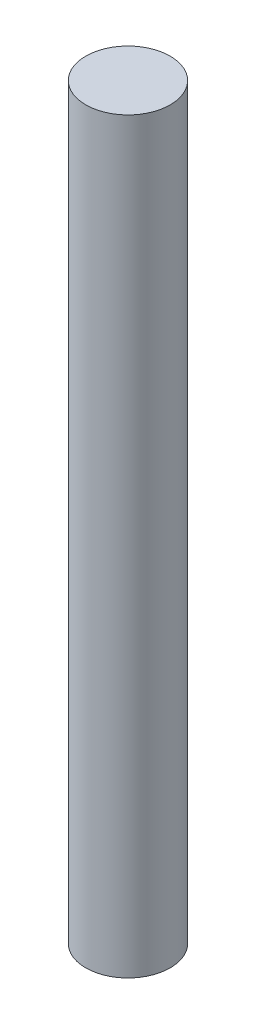
SolidWorks part; units mm, degrees
ref_plane "Alzado" through (0, 0, 0) normal (0, 0, 1) x (1, 0, 0)
ref_plane "Planta" through (0, 0, 0) normal (0, 1, 0) x (1, 0, 0)
ref_plane "Vista lateral" through (0, 0, 0) normal (1, 0, 0) x (0, 0, -1)
sketch "Croquis1" plane through (0, 0, 0) normal (0, 1, 0) x (1, 0, 0)
  circle A0 centre (0, 0) radius 4
  dimension "D1" = 8
extrude "Saliente-Extruir1" add sketch "Croquis1" along normal blind 100
ref_plane "Plano1" through (1.8651, 0, 3.5386) normal (0.4663, 0, 0.8846) x (0.8846, 0, -0.4663)
ref_plane "Plano2" through (1.8651, 0, 3.5386) normal (0.4663, 0, 0.8846) x (0.8846, 0, -0.4663)
sketch "Croquis2" plane through (1.8651, 0, 3.5386) normal (0.4663, 0, 0.8846) x (0.8846, 0, -0.4663)
  line L7 (-8.8187, 29.1961) -> (9.15, 29.1961)
  line L8 (-8.8187, 29.1961) -> (-8.8187, -2.457)
  line L9 (-8.8187, -2.457) -> (9.15, -2.457)
  line L10 (9.15, 29.1961) -> (9.15, -2.457)
extrude "Cortar-Extruir1" cut sketch "Croquis2" against normal blind 23
